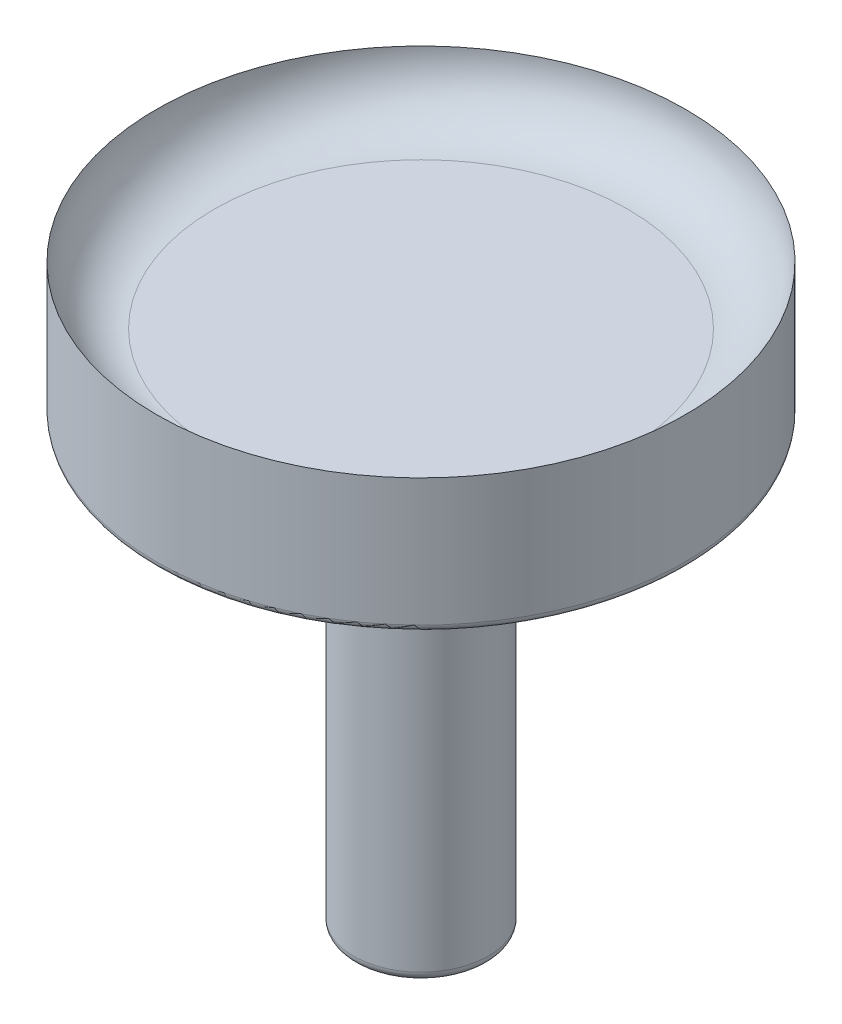
SolidWorks part; units mm, degrees
material "Polyetheretherketone (PEEK)"
ref_plane "Front Plane" through (0, 0, 0) normal (0, 0, 1) x (1, 0, 0)
ref_plane "Top Plane" through (0, 0, 0) normal (0, 1, 0) x (1, 0, 0)
ref_plane "Right Plane" through (0, 0, 0) normal (1, 0, 0) x (0, 0, -1)
sketch "Sketch1" plane through (0, 0, 0) normal (0, 0, 1) x (1, 0, 0)
  line L0 (0, -87.5279) -> (0, 23.7823) construction
  line L1 (0, 0) -> (-55, 0) construction
  line L2 (-55, 0) -> (-55, 18)
  line L3 (-55, 0) -> (-55, -8.5)
  line L4 (-43, 6) -> (0, 6)
  line L5 (0, 6) -> (0, 0)
  line L6 (-53.5, -10) -> (-52.5, -10)
  line L7 (-51, -8.5) -> (-51, -8)
  line L8 (-14, -2.75) -> (-14, -100)
  line L9 (-45, -2) -> (-14.75, -2)
  line L10 (0, -2) -> (0, 0)
  line L11 (-4, -2) -> (0, -2)
  line L12 (-10, -100) -> (-10, -96)
  line L13 (-4, -86) -> (0, -86)
  line L14 (0, -86) -> (0, -90)
  line L15 (0, -90) -> (-4, -90)
  line L16 (-4, -46) -> (0, -46)
  line L17 (-10, -36) -> (-10, -8)
  line L18 (0, -42) -> (-4, -42)
  line L19 (0, -42) -> (0, -46)
  line L20 (-10, -80) -> (-10, -52)
  arc A0 (-55, 18) -> (-43, 6) centre (-43, 18) ccw
  arc A1 (-51, -8) -> (-45, -2) centre (-45, -8) cw
  arc A2 (-55, -8.5) -> (-53.5, -10) centre (-53.5, -8.5) ccw
  arc A3 (-4, -2) -> (-10, -8) centre (-4, -8) ccw
  arc A4 (-14, -100) -> (-10, -100) centre (-12, -100) ccw
  arc A5 (-14, -2.75) -> (-14.75, -2) centre (-14.75, -2.75) ccw
  arc A6 (-4, -90) -> (-10, -96) centre (-4, -96) ccw
  arc A7 (-10, -80) -> (-4, -86) centre (-4, -80) ccw
  arc A8 (-10, -36) -> (-4, -42) centre (-4, -36) ccw
  arc A9 (-4, -46) -> (-10, -52) centre (-4, -52) ccw
  arc A10 (-52.5, -10) -> (-51, -8.5) centre (-52.5, -8.5) ccw
  point P6 (-12, -102)
  dimension "D3" = 1.5
  dimension "D5" = 40
  dimension "D12" = 12
  dimension "D13" = 12
  dimension "D14" = 12
  dimension "D15" = 12
  dimension "D16" = 12
  dimension "D17" = 6
  dimension "D18" = 12
  dimension "D20" = 1.5
  dimension "D4" = 100
  dimension "D21" = 1.5
  dimension "D1" = 55
  dimension "D2" = 14
  dimension "D6" = 2
  dimension "D7" = 6
  dimension "D8" = 10
  dimension "D9" = 4
  dimension "D10" = 4
  dimension "D11" = 84
  dimension "D19" = 4
  dimension "D22" = 10
revolve "Revolve1" add sketch "Sketch1" angle 360 about L0
ref_plane "Plane2" through (0, -90, 0) normal (0, -1, 0) x (-1, 0, 0)
sketch "Sketch3" plane through (0, -90, 0) normal (0, -1, 0) x (-1, 0, 0)
  line L0 (0, 0) -> (14.3256, 0) construction
  line L1 (0, 0) -> (10, 0)
  line L2 (0, 0) -> (-5, 8.6603)
  line L3 (0, 0) -> (-5, -8.6603)
  line L4 (-6.2425, 7.8123) -> (-1.7321, 0)
  line L5 (-1.7321, 0) -> (-6.2425, -7.8123)
  line L6 (-3.6444, 9.3123) -> (0.866, 1.5)
  line L7 (0.866, 1.5) -> (9.8869, 1.5)
  line L8 (9.8869, -1.5) -> (0.866, -1.5)
  line L9 (0.866, -1.5) -> (-3.6444, -9.3123)
  circle A0 centre (0, 0) radius 10
  arc A1 (-5.6219, 6.7375) -> (-7.2089, 6.9305) centre (-6.488, 6.2375) ccw
  arc A2 (-2.3976, 9.7083) -> (-3.0239, 8.2375) centre (-2.1578, 8.7375) ccw
  arc A3 (8.6458, 1.5) -> (9.6065, 2.7778) centre (8.6458, 2.5) ccw
  arc A4 (9.6065, -2.7778) -> (8.6458, -1.5) centre (8.6458, -2.5) ccw
  arc A5 (-3.0239, -8.2375) -> (-2.3976, -9.7083) centre (-2.1578, -8.7375) ccw
  arc A6 (-7.2089, -6.9305) -> (-5.6219, -6.7375) centre (-6.488, -6.2375) ccw
  arc A7 (-2.3094, -1) -> (-2.3094, 1) centre (-4.0415, 0) ccw
  arc A8 (0.2887, 2.5) -> (2.0207, 1.5) centre (2.0207, 3.5) ccw
  arc A9 (2.0207, -1.5) -> (0.2887, -2.5) centre (2.0207, -3.5) ccw
  point P40 (1.0207, 1.7679)
  dimension "D1" = 20
  dimension "D10" = 2
  dimension "D12" = 2
  dimension "D13" = 1
  dimension "D14" = 1
  dimension "D15" = 1
  dimension "D16" = 1
  dimension "D17" = 1
  dimension "D18" = 1
  dimension "D2" = 120
  dimension "D3" = 120
  dimension "D4" = 1.5
  dimension "D5" = 1.5
  dimension "D6" = 1.5
  dimension "D7" = 1.5
  dimension "D8" = 1.5
  dimension "D9" = 1.5
  dimension "D11" = 2
extrude "Cut-Extrude1" cut sketch "Sketch3" along normal blind 10 contours L6 A8 L7 A3 A0 A2 | L8 A9 L9 A5 A0 A4 | L5 A7 L4 A1 A0 A6 region at (-3.1908, -90, -5.5265) region at (-3.1908, -90, 5.5265) region at (6.3815, -90, 0)
extrude "Cut-Extrude2" cut sketch "Sketch3<3>" against normal blind 70 contours L5 A7 L4 A1 A0 A6 | L8 A9 L9 A5 A0 A4 | L6 A8 L7 A3 A0 A2 region at (-3.1908, -90, -5.5265) region at (-3.1908, -90, 5.5265) region at (6.3815, -90, 0)
sketch "Sketch3<3>" plane through (0, -90, 0) normal (0, -1, 0) x (-1, 0, 0) same geometry as "Sketch3"
